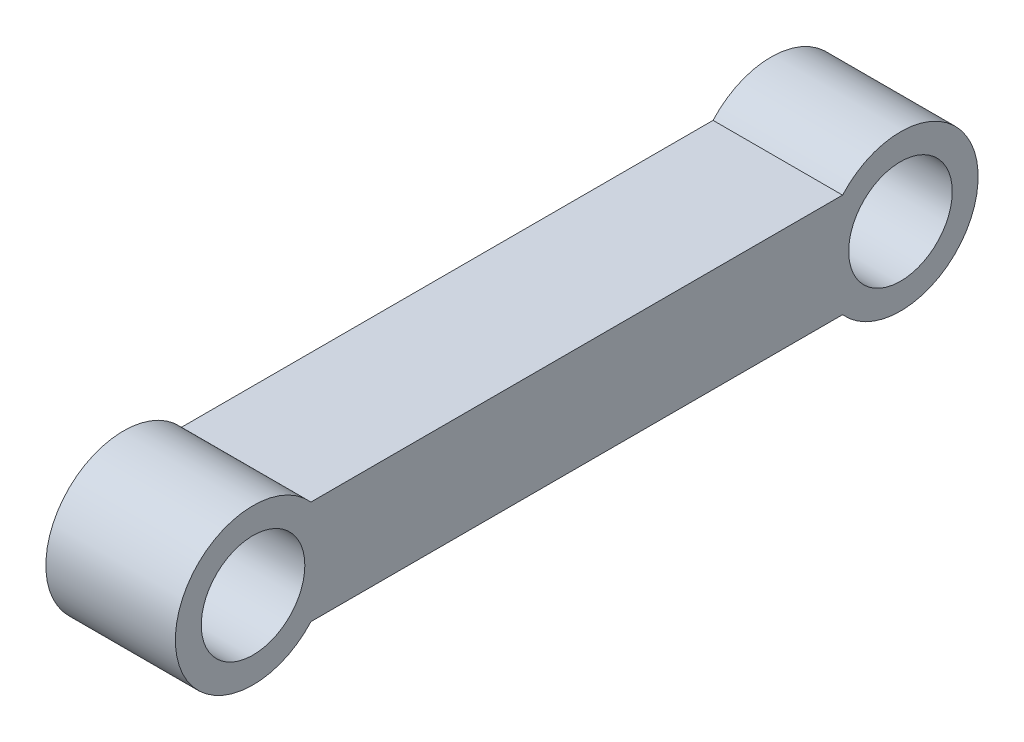
SolidWorks part; units mm, degrees
material "Thornel Mat VMA"
ref_plane "Front Plane" through (0, 0, 0) normal (0, 0, 1) x (1, 0, 0)
ref_plane "Top Plane" through (0, 0, 0) normal (0, 1, 0) x (1, 0, 0)
ref_plane "Right Plane" through (0, 0, 0) normal (1, 0, 0) x (0, 0, -1)
sketch "LinkFrame" plane through (0, 0, 0) normal (1, 0, 0) x (0, 0, -1)
  line L0 (-240.3455, -226.2633) -> (259.6545, -226.2633) construction
  line L1 (-195.6242, -186.2633) -> (214.9331, -186.2633)
  line L2 (-195.6242, -266.2633) -> (214.9331, -266.2633)
  arc A1 (214.9331, -266.2633) -> (214.9331, -186.2633) centre (259.6545, -226.2633) ccw
  arc A2 (-195.6242, -186.2633) -> (-195.6242, -266.2633) centre (-240.3455, -226.2633) ccw
  circle A5 centre (-240.3455, -226.2633) radius 40
  circle A6 centre (259.6545, -226.2633) radius 40
  dimension "D1" = 120
  dimension "D2" = 120
  dimension "D5" = 80
  dimension "D6" = 80
  dimension "D3" = 500
  dimension "D4" = 80
  dimension "D7" = 44.7214
  dimension "D8" = 44.7214
extrude "Boss-Extrude1" add sketch "LinkFrame" along normal blind 100
equation "\"D1@LinkFrame\" = 1.5 * \"HoleMountDiameter@PrintingPress.Assembly\""
equation "\"D2@LinkFrame\" = 1.5 * \"HoleMountDiameter@PrintingPress.Assembly\""
equation "\"LinkLength\" = 50cm"
equation "\"D3@LinkFrame\" = \"LinkLength\""
equation "\"D4@LinkFrame\" = \"HoleMountDiameter@PrintingPress.Assembly\""
equation "\"D5@LinkFrame\"=\"HoleMountDiameter@PrintingPress.Assembly\""
equation "\"D6@LinkFrame\"=\"HoleMountDiameter@PrintingPress.Assembly\""
equation "\"D1@Boss-Extrude1\"=\"RivetLength@PrintingPress.Assembly\""
